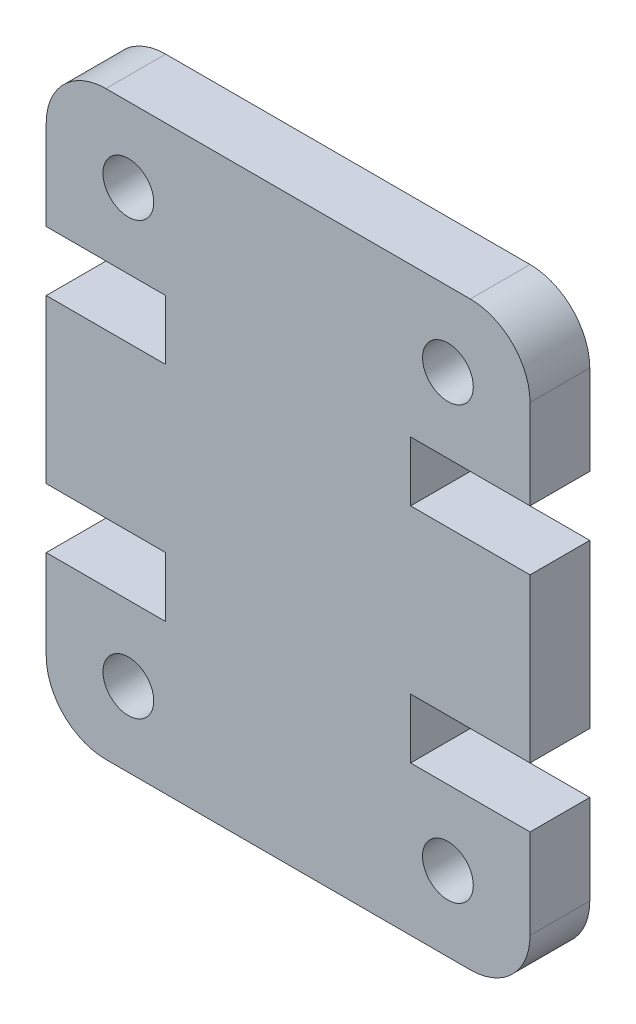
SolidWorks part; units mm, degrees
ref_plane "Front Plane" through (0, 0, 0) normal (0, 0, 1) x (1, 0, 0)
ref_plane "Top Plane" through (0, 0, 0) normal (0, 1, 0) x (1, 0, 0)
ref_plane "Right Plane" through (0, 0, 0) normal (1, 0, 0) x (0, 0, -1)
sketch "Sketch2" plane through (0, 0, 0) normal (0, 0, 1) x (1, 0, 0)
  line L0 (0, 7) -> (0, 12.455)
  line L1 (2, 0) -> (14.2, 0)
  line L2 (16.2, 5) -> (16.2, 2)
  line L3 (0, 9.7275) -> (16.2, 9.7275) construction
  line L4 (12.2, 5) -> (16.2, 5)
  line L5 (16.2, 7) -> (12.2, 7)
  line L6 (12.2, 7) -> (12.2, 5)
  line L7 (16.2, 7) -> (16.2, 12.455)
  line L8 (4, 7) -> (4, 5)
  line L9 (0, 14.455) -> (0, 17.455)
  line L10 (0, 7) -> (4, 7)
  line L11 (4, 5) -> (0, 5)
  line L12 (4, 14.455) -> (0, 14.455)
  line L13 (0, 12.455) -> (4, 12.455)
  line L14 (4, 12.455) -> (4, 14.455)
  line L15 (12.2, 12.455) -> (12.2, 14.455)
  line L16 (16.2, 12.455) -> (12.2, 12.455)
  line L17 (12.2, 14.455) -> (16.2, 14.455)
  line L18 (16.2, 14.455) -> (16.2, 17.455)
  line L19 (0, 5) -> (0, 2)
  line L20 (8.1, 19.455) -> (8.1, 0) construction
  line L21 (2, 19.455) -> (14.2, 19.455)
  circle A0 centre (13.45, 2.5) radius 0.85
  arc A1 (16.2, 2) -> (14.2, 0) centre (14.2, 2) cw
  circle A2 centre (2.75, 16.955) radius 0.85
  arc A3 (0, 2) -> (2, 0) centre (2, 2) ccw
  arc A4 (0, 17.455) -> (2, 19.455) centre (2, 17.455) cw
  circle A5 centre (2.75, 2.5) radius 0.85
  arc A6 (16.2, 17.455) -> (14.2, 19.455) centre (14.2, 17.455) ccw
  circle A7 centre (13.45, 16.955) radius 0.85
  point P18 (8.1, 9.7275)
  dimension "D1" = 1.7
  dimension "D2" = 2
  dimension "D3" = 2.75
  dimension "D4" = 8.1
  dimension "D5" = 2.5
  dimension "D8" = 9.7275
  dimension "D6" = 5
extrude "Boss-Extrude1" add sketch "Sketch2" along normal blind 4
sketch "Sketch3" plane through (0, 0, 4) normal (0, 0, 1) x (1, 0, 0)
  line L0 (0, 0) -> (16.2, 0)
  line L1 (16.2, 0) -> (16.2, 19.455)
  line L2 (16.2, 19.455) -> (0, 19.455)
  line L3 (0, 19.455) -> (0, 0)
extrude "Cut-Extrude1" cut sketch "Sketch3" against normal blind 2
equation "\"D4@Sketch2\"= \"fingerWidth@parametersSketch@prostheticParameters.SLDPRT\" / 2'Finger Width"
equation "\"D8@Sketch2\"= ( ( \"HL@parametersSketch@prostheticParameters.SLDPRT\" * 0.143 ) - 3 - 4 ) / 2 'MIP Length -SiliconeDIP-SiliconeMIP"
equation "\"D1@Sketch2\"= 1.5 + \"tol1@parametersSketch@prostheticParameters.SLDPRT\""
